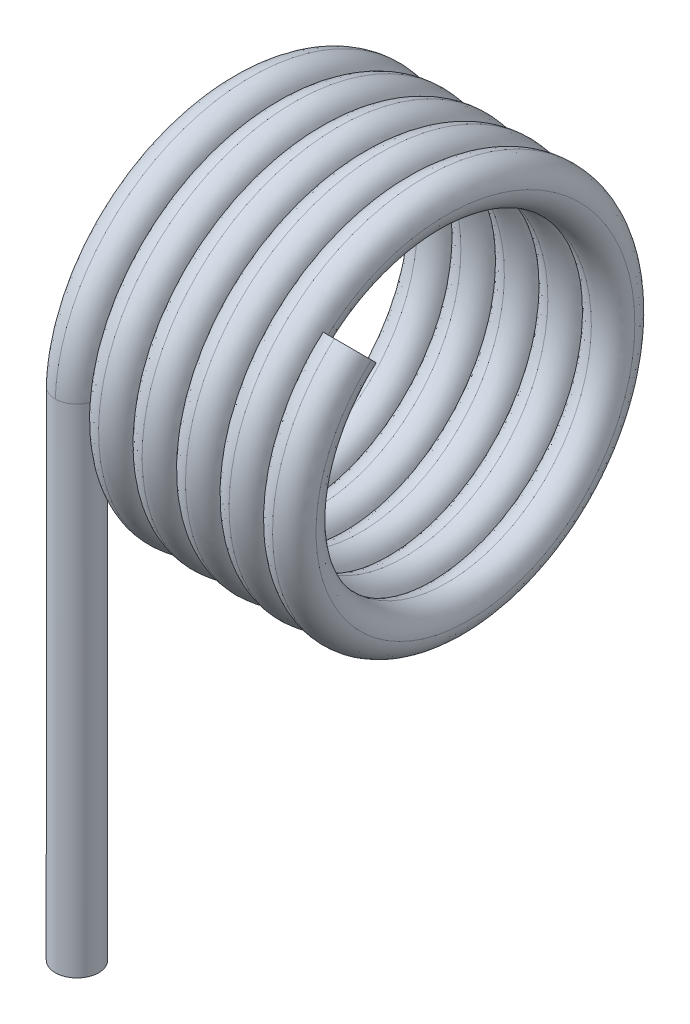
SolidWorks part; units mm, degrees
ref_plane "Front Plane" through (0, 0, 0) normal (0, 0, 1) x (1, 0, 0)
ref_plane "Top Plane" through (0, 0, 0) normal (0, 1, 0) x (1, 0, 0)
ref_plane "Right Plane" through (0, 0, 0) normal (1, 0, 0) x (0, 0, -1)
sketch "Sketch3" plane through (0, 0, 0) normal (1, 0, 0) x (0, 0, -1)
  circle A0 centre (0, 0) radius 21.74
  dimension "D1" = 43.48
curve "Helix/Spiral1" pitch 5.5562 height 28.4758 radius 21.74 left hand yes centre (0, 0, 0) axis (1, 0, 0) start towards (0, 0, 1)
sketch "Sketch4" plane through (0, 0, 0) normal (0, 1, 0) x (1, 0, 0)
  circle A0 centre (0, -21.74) radius 2.7781
  spline S0 degree 3 poles (0, -21.74) (0.09, -21.74) (0.2714, -21.0531) (0.5424, -18.0581) (0.8136, -13.3779) (1.0848, -7.4494) (1.356, -0.8257) (1.6272, 5.875) (1.8984, 12.0275) (2.1696, 17.0576) (2.4408, 20.496) (2.712, 22.0217) (2.9832, 21.4924) (3.2544, 18.9575) (3.5256, 14.6536) (3.7968, 8.9822) (4.068, 2.4726) (4.3392, -4.2678) (4.6104, -10.6098) (4.8816, -15.9618) (5.1528, -19.8243) (5.424, -21.8368) (5.6952, -21.8116) (5.9664, -19.7509) (6.2376, -15.8472) (6.5088, -10.4647) (6.7799, -4.1056) (7.0511, 2.6366) (7.3223, 9.1328) (7.5935, 14.7767) (7.8647, 19.0417) (8.1359, 21.5298) (8.4071, 22.0088) (8.6783, 20.4339) (8.9495, 16.9523) (9.2207, 11.8886) (9.4919, 5.7156) (9.7631, -0.9908) (10.0343, -7.6047) (10.3055, -13.509) (10.5767, -18.1527) (10.8479, -21.1024) (11.1191, -22.0828) (11.3903, -21.0026) (11.6615, -17.9625) (11.9327, -13.2461) (12.2039, -7.2937) (12.4751, -0.6606) (12.7463, 6.0341) (13.0175, 12.1657) (13.2887, 17.1621) (13.5599, 20.5569) (13.8311, 22.0334) (14.1023, 21.4539) (14.3735, 18.8723) (14.6447, 14.5296) (14.9159, 8.831) (15.1871, 2.3084) (15.4583, -4.4297) (15.7295, -10.7544) (16.0007, -16.0755) (16.2719, -19.8965) (16.5431, -21.8608) (16.8143, -21.7851) (17.0855, -19.6765) (17.3567, -15.7317) (17.6279, -10.3189) (17.8991, -3.9432) (18.1703, 2.8006) (18.4415, 9.2829) (18.7127, 14.8991) (18.9839, 19.1248) (19.2551, 21.5659) (19.5263, 21.9946) (19.7974, 20.3707) (20.0686, 16.8459) (20.3398, 11.7491) (20.611, 5.5559) (20.8822, -1.1558) (21.1534, -7.7596) (21.4246, -13.6393) (21.6958, -18.2462) (21.967, -21.1505) (22.2382, -22.081) (22.5094, -20.951) (22.7806, -17.8659) (23.0518, -13.1136) (23.323, -7.1376) (23.5942, -0.4955) (23.8654, 6.1928) (24.1366, 12.3032) (24.4078, 17.2655) (24.679, 20.6167) (24.9502, 22.0439) (25.2214, 21.4141) (25.4926, 18.786) (25.7638, 14.4048) (26.035, 8.6794) (26.3062, 2.144) (26.5774, -4.5914) (26.8486, -10.8984) (27.1198, -16.1883) (27.391, -19.9676) (27.6622, -21.8838) (27.9334, -21.7567) (28.2044, -19.6038) (28.3857, -16.9378) (28.4758, -15.3725) knots 0 0 0 0 0.009524 0.019048 0.028571 0.038095 0.047619 0.057143 0.066667 0.07619 0.085714 0.095238 0.104762 0.114286 0.12381 0.133333 0.142857 0.152381 0.161905 0.171429 0.180952 0.190476 0.2 0.209524 0.219048 0.228571 0.238095 0.247619 0.257143 0.266667 0.27619 0.285714 0.295238 0.304762 0.314286 0.32381 0.333333 0.342857 0.352381 0.361905 0.371429 0.380952 0.390476 0.4 0.409524 0.419048 0.428571 0.438095 0.447619 0.457143 0.466667 0.47619 0.485714 0.495238 0.504762 0.514286 0.52381 0.533333 0.542857 0.552381 0.561905 0.571429 0.580952 0.590476 0.6 0.609524 0.619048 0.628571 0.638095 0.647619 0.657143 0.666667 0.67619 0.685714 0.695238 0.704762 0.714286 0.72381 0.733333 0.742857 0.752381 0.761905 0.771429 0.780952 0.790476 0.8 0.809524 0.819048 0.828571 0.838095 0.847619 0.857143 0.866667 0.87619 0.885714 0.895238 0.904762 0.914286 0.92381 0.933333 0.942857 0.952381 0.961905 0.971429 0.980952 0.990476 1 1 1 1 construction
  point P4 (0, -21.74)
  point P5 (0, -21.74)
  point P6 (0, -21.74)
  point P7 (0, -21.74)
  point P8 (0, 0)
  point P9 (0, 0)
  dimension "D1" = 5.5562
sweep "Sweep1" add profiles "Sketch4" path "Helix/Spiral1"
sketch "Sketch5" plane through (0, 0, 0) normal (0, -1, 0) x (1, 0, 0)
  circle A0 centre (0, 21.74) radius 2.7781
  arc A1 (2.7781, 21.74) -> (0, 24.5181) centre (0, 21.74) ccw construction
extrude "Boss-Extrude1" add sketch "Sketch5" along normal blind 63.5
